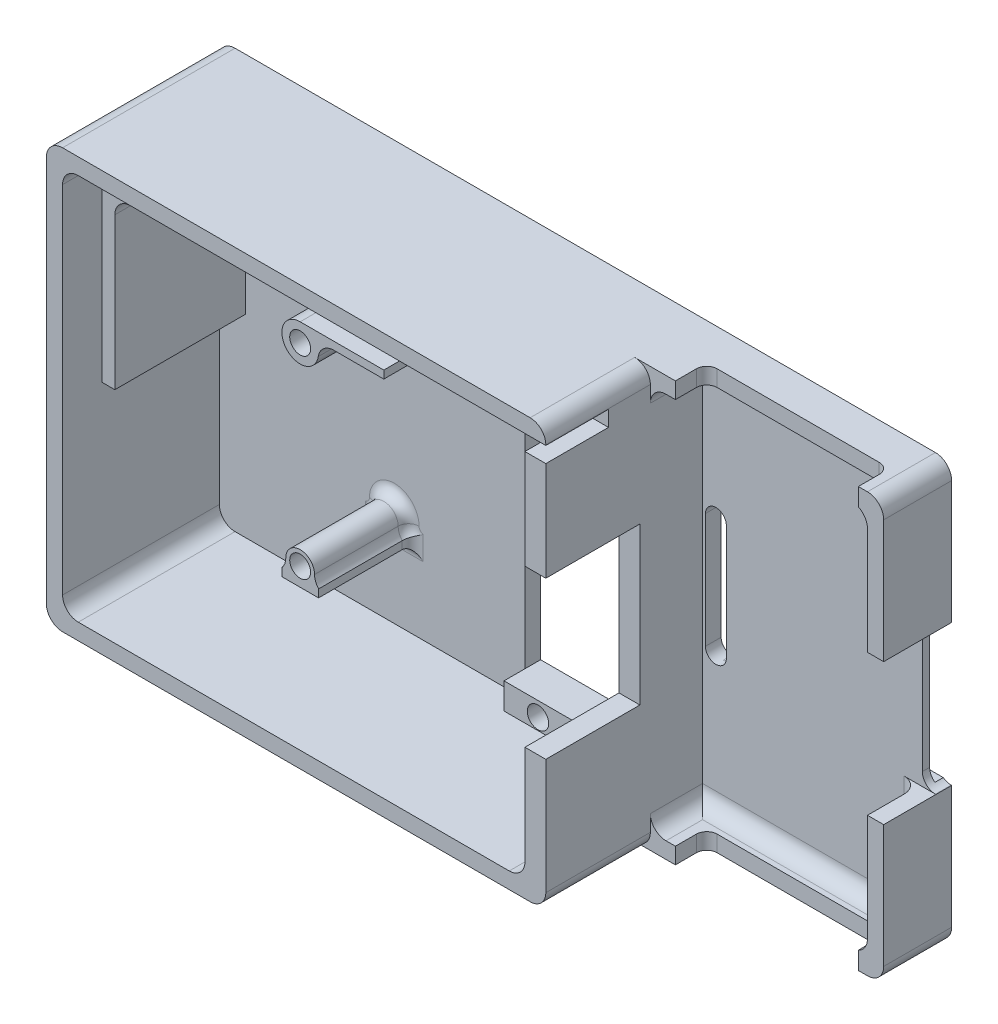
SolidWorks part; units mm, degrees
ref_plane "Front Plane" through (0, 0, 0) normal (0, 0, 1) x (1, 0, 0)
ref_plane "Top Plane" through (0, 0, 0) normal (0, 1, 0) x (1, 0, 0)
ref_plane "Right Plane" through (0, 0, 0) normal (1, 0, 0) x (0, 0, -1)
sketch "Sketch1" plane through (0, 0, 0) normal (0, 0, 1) x (1, 0, 0)
  line L0 (0, 0) -> (-50000, 0) construction
  line L1 (-15, 32) -> (15, 32)
  line L2 (-15, 32) -> (-15, -32)
  line L3 (-15, -32) -> (15, -32)
  line L4 (15, 32) -> (15, -32)
  line L5 (-15, 32) -> (15, -32) construction
  line L6 (-15, -32) -> (15, 32) construction
  line L7 (0, 0) -> (0, 50000) construction
  line L8 (-40, 18.5) -> (-40, -18.5) construction
  line L9 (-8.5, -34.8) -> (8.5, -34.8) construction
  line L10 (-8.5, -34.8) -> (-8.5, 34.8) construction
  line L11 (-8.5, 34.8) -> (8.5, 34.8) construction
  line L12 (8.5, -34.8) -> (8.5, 34.8) construction
  line L13 (-8.5, -34.8) -> (8.5, 34.8) construction
  line L14 (-8.5, 34.8) -> (8.5, -34.8) construction
  line L15 (-76.4572, -40) -> (63.5428, -40)
  line L16 (-76.4572, -40) -> (-76.4572, 40)
  line L17 (-76.4572, 40) -> (63.5428, 40)
  line L18 (63.5428, -40) -> (63.5428, 40)
  line L19 (-76.4572, -40) -> (63.5428, 40) construction
  line L20 (-76.4572, 40) -> (63.5428, -40) construction
  line L21 (21.5428, -11) -> (21.5428, 11) construction
  line L22 (-57.5, -25) -> (-22.5, -25) construction
  line L23 (-57.5, -25) -> (-57.5, 25) construction
  line L24 (-57.5, 25) -> (-22.5, 25) construction
  line L25 (-22.5, -25) -> (-22.5, 25) construction
  line L26 (-57.5, -25) -> (-22.5, 25) construction
  line L27 (-57.5, 25) -> (-22.5, -25) construction
  line L29 (19.5428, -11) -> (19.5428, 11)
  line L30 (23.5428, -11) -> (23.5428, 11)
  circle A0 centre (-8.5, 34.8) radius 1.7
  circle A1 centre (8.5, 34.8) radius 1.7
  circle A2 centre (8.5, -34.8) radius 1.7
  circle A3 centre (-8.5, -34.8) radius 1.7
  circle A4 centre (-40, 18.5) radius 1.85
  circle A5 centre (-40, -18.5) radius 1.85
  arc A6 (19.5428, -11) -> (23.5428, -11) centre (21.5428, -11) ccw
  arc A7 (23.5428, 11) -> (19.5428, 11) centre (21.5428, 11) ccw
  point P0 (0, 0)
  point P10 (0, 0)
  point P19 (-6.4572, 0)
  point P28 (-40, 0)
  point P29 (-40, 0)
  point P38 (21.5428, 0)
  dimension "D3" = 80
  dimension "D5" = 18.5
  dimension "D8" = 2
  dimension "D10" = 3.4
  dimension "D11" = 3.4
  dimension "D12" = 3.7
  dimension "D1" = 30
  dimension "D2" = 64
  dimension "D4" = 140
  dimension "D6" = 40
  dimension "D7" = 22
  dimension "D9" = 42
extrude "Boss-Extrude1" add sketch "Sketch1" along normal blind 3
sketch "Sketch2" plane through (0, 0, 3) normal (0, 0, 1) x (1, 0, 0)
  line L0 (63.5428, -11) -> (63.5428, 11) construction
  line L1 (63.5428, -40) -> (63.5428, 40) construction
  line L3 (61.0428, -11) -> (61.0428, 11)
  line L4 (66.0428, -11) -> (66.0428, 11)
  arc A0 (61.0428, -11) -> (66.0428, -11) centre (63.5428, -11) ccw
  arc A1 (66.0428, 11) -> (61.0428, 11) centre (63.5428, 11) ccw
  point P6 (63.5428, 0)
  dimension "D1" = 2.5
extrude "lipo strap" cut sketch "Sketch2" against normal up to surface (3 mm away) up to face at (-38.15, 18.5, 0)
fillet "Fillet1" radius 3 4 edges at (63.5428, -40, 1.5) (-76.4572, -40, 1.5) (63.5428, 40, 1.5) (-76.4572, 40, 1.5)
sketch "Sketch3" plane through (0, 0, 3) normal (0, 0, 1) x (1, 0, 0)
  line L25 (60.5428, 13.5) -> (63.6428, 13.5)
  line L26 (60.5428, -13.5) -> (63.6428, -13.5)
  line L30 (60.5428, 13.5) -> (60.5428, 37)
  line L31 (60.5428, -37) -> (60.5428, -13.5)
  line L32 (-73.4572, -37) -> (60.5428, -37)
  line L33 (-73.4572, 37) -> (-73.4572, -37)
  line L34 (60.5428, 37) -> (-73.4572, 37)
  line L35 (60.5428, 13.5) -> (60.5428, 34)
  line L36 (60.5428, -34) -> (60.5428, -13.5)
  line L37 (-70.4572, -37) -> (57.5428, -37)
  line L38 (-73.4572, 34) -> (-73.4572, -34)
  line L39 (57.5428, 37) -> (-70.4572, 37)
  line L67 (63.6428, 13.5) -> (63.6428, 37)
  line L68 (63.6428, -37) -> (63.6428, -13.5)
  line L69 (-73.4572, -40.1) -> (60.5428, -40.1)
  line L70 (-76.5572, 37) -> (-76.5572, -37)
  line L71 (60.5428, 40.1) -> (-73.4572, 40.1)
  line L72 (63.6428, 13.5) -> (63.6428, 37)
  line L73 (63.6428, -37) -> (63.6428, -13.5)
  line L74 (-73.4572, -40.1) -> (60.5428, -40.1)
  line L75 (-76.5572, 37) -> (-76.5572, -37)
  line L76 (60.5428, 40.1) -> (-73.4572, 40.1)
  arc A40 (60.5428, -34) -> (57.5428, -37) centre (57.5428, -34) cw
  arc A41 (-70.4572, -37) -> (-73.4572, -34) centre (-70.4572, -34) cw
  arc A42 (-73.4572, 34) -> (-70.4572, 37) centre (-70.4572, 34) cw
  arc A43 (60.5428, 34) -> (57.5428, 37) centre (57.5428, 34) ccw
  arc A44 (63.6428, 37) -> (60.5428, 40.1) centre (60.5428, 37) ccw
  arc A45 (60.5428, -40.1) -> (63.6428, -37) centre (60.5428, -37) ccw
  arc A46 (-76.5572, -37) -> (-73.4572, -40.1) centre (-73.4572, -37) ccw
  arc A47 (-73.4572, 40.1) -> (-76.5572, 37) centre (-73.4572, 37) ccw
  arc A48 (63.6428, 37) -> (60.5428, 40.1) centre (60.5428, 37) ccw
  arc A49 (60.5428, -40.1) -> (63.6428, -37) centre (60.5428, -37) ccw
  arc A50 (-76.5572, -37) -> (-73.4572, -40.1) centre (-73.4572, -37) ccw
  arc A51 (-73.4572, 40.1) -> (-76.5572, 37) centre (-73.4572, 37) ccw
  dimension "D3" = 3
  dimension "D4" = 3
  dimension "D2" = 0.1
  dimension "D1" = 3
extrude "wall" add sketch "Sketch3" along normal blind 30 and the other way up to surface (3 mm away) other way up to face at (16.3732, 0, 0)
sketch "Sketch4" plane through (0, 0, 3) normal (0, 0, 1) x (1, 0, 0)
  line L1 (-15, 38.0778) -> (15, 38.0778)
  line L2 (-15, 38.0778) -> (-15, 32)
  line L3 (-15, 32) -> (15, 32)
  line L4 (15, 38.0778) -> (15, 32)
  line L5 (-15, 38.0778) -> (15, 32) construction
  line L6 (-15, 32) -> (15, 38.0778) construction
  line L7 (15, -32) -> (15, 32) construction
  line L8 (0, 0) -> (50000, 0) construction
  line L9 (-15, -32) -> (15, -38.0778) construction
  line L10 (-15, -38.0778) -> (15, -32) construction
  line L11 (15, -38.0778) -> (15, -32)
  line L12 (-15, -32) -> (15, -32)
  line L13 (-15, -38.0778) -> (-15, -32)
  line L14 (-15, -38.0778) -> (15, -38.0778)
  circle A0 centre (-8.5, 34.8) radius 2.05
  circle A1 centre (8.5, 34.8) radius 2.05
  circle A2 centre (8.5, -34.8) radius 2.05
  circle A3 centre (-8.5, -34.8) radius 2.05
  point P6 (0, 35.0389)
  point P24 (0, -35.0389)
  dimension "D1" = 4.1
  dimension "D2" = 4.1
extrude "servo bolts" add sketch "Sketch4" along normal blind 4
sketch "Sketch5" plane through (0, 0, 3) normal (0, 0, 1) x (1, 0, 0)
  line L0 (0, 0) -> (50000, 0) construction
  line L2 (19.3834, 52.5) -> (60.2103, 52.5) construction
  line L3 (19.3834, 52.5) -> (19.3834, -52.5) construction
  line L4 (19.3834, -52.5) -> (60.2103, -52.5) construction
  line L5 (60.2103, 52.5) -> (60.2103, -52.5) construction
  line L6 (19.3834, 52.5) -> (60.2103, -52.5) construction
  line L7 (19.3834, -52.5) -> (60.2103, 52.5) construction
  line L8 (19, -37) -> (15, -37)
  line L9 (19, -37) -> (19, 37)
  line L10 (19, 37) -> (15, 37)
  line L11 (15, -37) -> (15, 37)
  line L12 (19, -37) -> (15, 37) construction
  line L13 (19, 37) -> (15, -37) construction
  point P3 (39.7968, 0)
  point P8 (17, 0)
  dimension "D1" = 4
extrude "lipo wall" add sketch "Sketch5" along normal up to surface (30 mm away) up to face at (7.2528, 0, 33)
sketch "Sketch6" plane through (0, 0, 3) normal (0, 0, 1) x (1, 0, 0)
  circle A0 centre (-40, 18.5) radius 2
  circle A1 centre (-40, 18.5) radius 3.5
  circle A2 centre (-40, -18.5) radius 2
  circle A3 centre (-40, -18.5) radius 2.75
  dimension "D1" = 7
  dimension "D2" = 5.5
  dimension "D3" = 4
  dimension "D4" = 4
extrude "PCB standoff" add sketch "Sketch6" along normal blind 18
sketch "Sketch7" plane through (0, 0, 3) normal (0, 0, 1) x (1, 0, 0)
  line L0 (-40, 18.5) -> (-40, -49981.5) construction
  line L2 (-57.5, -25) -> (-22.5, -25) construction
  line L3 (-57.5, -25) -> (-57.5, 25) construction
  line L4 (-57.5, 25) -> (-22.5, 25) construction
  line L5 (-22.5, -25) -> (-22.5, 25) construction
  line L6 (-57.5, -25) -> (-22.5, 25) construction
  line L7 (-57.5, 25) -> (-22.5, -25) construction
  point P4 (-40, 0)
sketch "Sketch8" plane through (0, 0, 33) normal (0, 0, 1) x (1, 0, 0)
  line L0 (19, 37) -> (57.5428, 37) construction
  line L1 (15, 34) -> (19, 34)
  line L2 (15, 34) -> (15, 37)
  line L3 (15, 37) -> (19, 37)
  line L4 (19, 34) -> (19, 37)
  line L5 (15, 34) -> (19, 37) construction
  line L6 (15, 37) -> (19, 34) construction
  line L7 (19, 37) -> (19, -37) construction
  point P0 (17, 35.5)
  dimension "D1" = 3
extrude "wire" cut sketch "Sketch8" against normal blind 12
sketch "Sketch9" plane through (0, 0, 33) normal (0, 0, 1) x (1, 0, 0)
  line L0 (0, 0) -> (50000, 0) construction
  line L2 (19, -37) -> (19, 37) construction
  line L3 (103.8935, 53.0966) -> (19, 53.0966)
  line L4 (103.8935, 53.0966) -> (103.8935, -53.0966)
  line L5 (103.8935, -53.0966) -> (19, -53.0966)
  line L6 (19, 53.0966) -> (19, -53.0966)
  line L7 (103.8935, 53.0966) -> (19, -53.0966) construction
  line L8 (103.8935, -53.0966) -> (19, 53.0966) construction
  point P3 (61.4467, 0)
extrude "Cut-Extrude3" cut sketch "Sketch9" against normal blind 20
fillet "Fillet2" radius 3 10 edges at (60.5428, -23.75, 3) (59.6641, -36.1213, 3) (60.5428, 23.75, 3) (59.6641, 36.1213, 3) (15, -37, 20) (15, 37, 14) (38.2714, -37, 3) (19, -37, 8) (38.2714, 37, 3) (19, 37, 8)
sketch "Sketch10" plane through (0, 0, 0) normal (0, 0, -1) x (-1, 0, 0)
  line L1 (-67.8085, 13) -> (-21.5428, 13)
  line L2 (-67.8085, 13) -> (-67.8085, -13)
  line L3 (-67.8085, -13) -> (-21.5428, -13)
  line L4 (-21.5428, 13) -> (-21.5428, -13)
  line L5 (-67.8085, 13) -> (-21.5428, -13) construction
  line L6 (-67.8085, -13) -> (-21.5428, 13) construction
  arc A0 (-23.5428, -11) -> (-19.5428, -11) centre (-21.5428, -11) ccw construction
  point P0 (-44.6757, 0)
extrude "Cut-Extrude4" cut sketch "Sketch10" against normal blind 1.6
sketch "Sketch11" plane through (0, 0, 3) normal (0, 0, 1) x (1, 0, 0)
  line L0 (-40, 200018.5) -> (-40, -249981.5) construction
  line L1 (-43.5225, -21.9959) -> (-36.4775, -21.9959)
  line L2 (-43.5225, -21.9959) -> (-43.5225, -20.5041)
  line L3 (-43.5225, -20.5041) -> (-36.4775, -20.5041)
  line L4 (-36.4775, -21.9959) -> (-36.4775, -20.5041)
  line L5 (-43.5225, -21.9959) -> (-36.4775, -20.5041) construction
  line L6 (-43.5225, -20.5041) -> (-36.4775, -21.9959) construction
  line L8 (-24, 20.5) -> (-40, 20.5)
  line L9 (-24, 20.5) -> (-24, 22)
  line L10 (-24, 22) -> (-40, 22)
  line L11 (-40, 20.5) -> (-40, 22)
  line L12 (-24, 20.5) -> (-40, 22) construction
  line L13 (-24, 22) -> (-40, 20.5) construction
  circle A0 centre (-40, -18.5) radius 2.75 construction
  circle A1 centre (-40, 18.5) radius 3.5 construction
  circle A2 centre (-40, 18.5) radius 2 construction
  point P0 (-40, -21.25)
  point P9 (-32, 21.25)
  point P14 (0, 0)
extrude "Boss-Extrude6" add sketch "Sketch11" along normal up to surface (18 mm away) up to face at (-36.5, 18.5, 21)
fillet "Fillet4" radius 3 3 edges at (-41.8831, -20.5041, 12) (-38.1169, -20.5041, 12) (-37.1277, 20.5, 12)
fillet "Fillet5" radius 2 11 edges at (-28.7887, 20.5, 3) (-32, 22, 3) (-42.6584, 16.2234, 3) (-37.0497, -19.5723, 3) (-43.5225, -21.25, 3) (-42.9503, -19.5723, 3) (-40, -15.75, 3) (-40, -21.9959, 3) (-36.4775, -21.25, 3) (-24, 21.25, 3) (-35.5287, 19.7787, 3)
fillet "Fillet6" radius 3 2 edges at (19, 40.1, 23) (19, -40.1, 23)
sketch "Sketch12" plane through (0, 0, 13) normal (0, 0, 1) x (1, 0, 0)
  line L0 (21.5428, 13) -> (21.5428, -13) construction
  line L2 (61.0428, 11) -> (61.0428, -11) construction
  line L3 (61.0428, 0) -> (21.5428, 0) construction
  line L4 (23.7928, -50) -> (58.7928, -50)
  line L5 (23.7928, -50) -> (23.7928, 50)
  line L6 (23.7928, 50) -> (58.7928, 50)
  line L7 (58.7928, -50) -> (58.7928, 50)
  line L8 (23.7928, -50) -> (58.7928, 50) construction
  line L9 (23.7928, 50) -> (58.7928, -50) construction
  point P4 (41.2928, 0)
  dimension "D1" = 35
extrude "Cut-Extrude5" cut sketch "Sketch12" against normal blind 6
fillet "Fillet7" radius 2 4 edges at (58.7928, 38.4136, 7) (58.7928, -38.4136, 7) (23.7928, -38.55, 7) (23.7928, 38.55, 7)
sketch "Sketch13" plane through (0, 0, 3) normal (0, 0, 1) x (1, 0, 0)
  line L6 (-70.9572, 34) -> (-70.9572, -34)
  line L7 (-15, 34.5) -> (-70.4572, 34.5)
  line L8 (-70.9572, 31.5) -> (-70.9572, 0.015)
  line L9 (-15, 34.5) -> (-67.9572, 34.5)
  line L12 (-70.9572, 0.015) -> (-68.4572, 0.015)
  line L13 (-15, 32) -> (-15, 34.5)
  line L14 (-68.4572, -34) -> (-68.4572, 32)
  line L15 (-68.4572, 32) -> (-15, 32)
  line L16 (-68.4572, 0.015) -> (-68.4572, 29)
  line L17 (-65.4572, 32) -> (-15, 32)
  arc A3 (-70.4572, 34.5) -> (-70.9572, 34) centre (-70.4572, 34) ccw
  arc A4 (-70.9572, 31.5) -> (-67.9572, 34.5) centre (-67.9572, 31.5) cw
  arc A6 (-68.4572, 29) -> (-65.4572, 32) centre (-65.4572, 29) cw
  dimension "D3" = 3
  dimension "D1" = 2.5
  dimension "D2" = 5
extrude "Boss-Extrude7" add sketch "Sketch13" along normal blind 25
sketch "Sketch14" plane through (0, 0, 33) normal (0, 0, 1) x (1, 0, 0)
  line L0 (15, -34) -> (15, 34) construction
  line L1 (4.9743, -15) -> (25.0257, -15)
  line L2 (4.9743, -15) -> (4.9743, 15)
  line L3 (4.9743, 15) -> (25.0257, 15)
  line L4 (25.0257, -15) -> (25.0257, 15)
  line L5 (4.9743, -15) -> (25.0257, 15) construction
  line L6 (4.9743, 15) -> (25.0257, -15) construction
  point P0 (15, 0)
  dimension "D1" = 30
extrude "Cut-Extrude6" cut sketch "Sketch14" against normal blind 18
equation "\"D4@Sketch6\"=\"D3@Sketch6\""
equation "\"D2@Sketch4\"=\"D1@Sketch4\""
